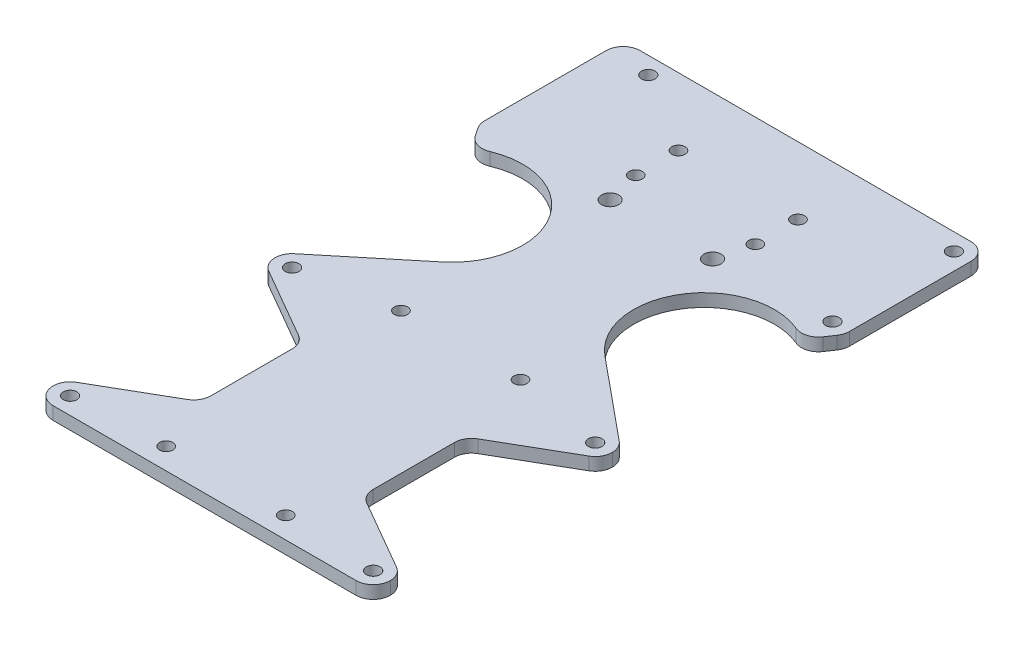
SolidWorks part; units mm, degrees
material "Thornel Mat VMA"
ref_plane "Front Plane" through (0, 0, 0) normal (0, 0, 1) x (1, 0, 0)
ref_plane "Top Plane" through (0, 0, 0) normal (0, 1, 0) x (1, 0, 0)
ref_plane "Right Plane" through (0, 0, 0) normal (1, 0, 0) x (0, 0, -1)
sketch "Sketch1" plane through (0, 0, 0) normal (0, 1, 0) x (1, 0, 0)
  line L0 (0, 0) -> (0, -82.5) construction
  line L1 (29.5, 0) -> (0, 0) construction
  line L19 (14, -27.5) -> (-14, -27.5) construction
  line L22 (14, -27.5) -> (14, 27.5) construction
  line L25 (14, 27.5) -> (-14, 27.5) construction
  line L28 (-14, -27.5) -> (-14, 27.5) construction
  line L38 (14, -27.5) -> (-14, 27.5) construction
  line L41 (47.5, 62.5) -> (-47.5, 62.5)
  line L44 (47.5, 62.5) -> (47.5, -87.5)
  line L47 (47.5, -87.5) -> (-47.5, -87.5)
  line L50 (-47.5, 62.5) -> (-47.5, -87.5)
  line L59 (-959, -57) -> (49041, -57) construction
  line L65 (14, 27.5) -> (-14, -27.5) construction
  line L66 (-14, 37.5) -> (14, 37.5) construction
  line L67 (-14, 37.5) -> (-14, 27.5) construction
  line L69 (14, 37.5) -> (14, 27.5) construction
  line L74 (-14, -27.5) -> (-14, -82.5) construction
  line L75 (-14, -82.5) -> (14, -82.5) construction
  line L76 (14, -82.5) -> (14, -27.5) construction
  line L94 (0, -82.5) -> (0, -87.5) construction
  circle A0 centre (29.5, 0) radius 16.5
  circle A22 centre (14, 27.5) radius 1.55
  circle A23 centre (14, -27.5) radius 1.55
  circle A24 centre (-14, -27.5) radius 1.55
  circle A25 centre (-14, 27.5) radius 1.55
  circle A76 centre (-14, 37.5) radius 1.55
  circle A77 centre (14, 37.5) radius 1.55
  circle A91 centre (-14, -82.5) radius 1.55
  circle A92 centre (14, -82.5) radius 1.55
  circle A99 centre (-29.5, 0) radius 16.5
  point P1 (0, -53.5)
  point P37 (29.5, 0)
  point P51 (0, 32.5)
  dimension "D1" = 33
  dimension "D6" = 25
  dimension "D7" = 5
  dimension "D10" = 3.1
  dimension "D12" = 55
  dimension "D15" = 10
  dimension "D19" = 28
  dimension "D20" = 29.5
  dimension "D3" = 95
  dimension "D14" = 55
extrude "凸台-拉伸1" add sketch "Sketch1" along normal blind 3 contours L41 L50 L47 L44 A23 A22 A0 region at (0, 0, 14.2195)
sketch "草图9" plane through (0, 0, 0) normal (0, 1, 0) x (1, 0, 0)
  line L0 (0, 35) -> (0, 0) construction
  line L1 (42.55, 7.5) -> (-42.55, 7.5) construction
  line L2 (42.55, 7.5) -> (42.55, 62.5) construction
  line L3 (42.55, 62.5) -> (-42.55, 62.5) construction
  line L4 (-42.55, 7.5) -> (-42.55, 62.5) construction
  line L5 (42.55, 7.5) -> (-42.55, 62.5) construction
  line L6 (42.55, 62.5) -> (-42.55, 7.5) construction
  line L7 (-32.84, 49.29) -> (38.74, 49.29) construction
  line L8 (38.74, 49.29) -> (38.74, 20.84) construction
  circle A0 centre (-14, 27.5) radius 1.55 construction
  circle A1 centre (38.74, 20.84) radius 1.6
  circle A2 centre (38.74, 49.29) radius 1.6
  circle A3 centre (-32.84, 49.29) radius 1.6
  point P0 (0, 35)
  dimension "D6" = 3.2
  dimension "D1" = 55
  dimension "D2" = 85.1
  dimension "D3" = 20
  dimension "D4" = 3.81
  dimension "D5" = 13.21
  dimension "D7" = 13.34
  dimension "D8" = 9.71
extrude "主控板固定孔" cut sketch "草图9" along normal up to next
sketch "草图10" plane through (0, 0, 0) normal (0, 1, 0) x (1, 0, 0)
  line L0 (0, 0) -> (0, -57.5) construction
  line L1 (35.5, -83.5) -> (-35.5, -83.5) construction
  line L2 (35.5, -83.5) -> (35.5, -31.5) construction
  line L3 (35.5, -31.5) -> (-35.5, -31.5) construction
  line L4 (-35.5, -83.5) -> (-35.5, -31.5) construction
  line L5 (35.5, -83.5) -> (-35.5, -31.5) construction
  line L6 (35.5, -31.5) -> (-35.5, -83.5) construction
  line L7 (47.5, -87.5) -> (-47.5, -87.5) construction
  circle A0 centre (35.5, -31.5) radius 1.6
  circle A1 centre (35.5, -83.5) radius 1.6
  circle A2 centre (-35.5, -31.5) radius 1.6
  circle A3 centre (-35.5, -83.5) radius 1.6
  point P0 (0, -57.5)
  dimension "D1" = 4
  dimension "D2" = 3.2
  dimension "D3" = 52
  dimension "D4" = 71
extrude "图传固定孔" cut sketch "草图10" along normal up to next
sketch "草图11" plane through (0, 0, 0) normal (0, 1, 0) x (1, 0, 0)
  line L0 (0, 0) -> (0, 22.5) construction
  line L1 (9, -22.5) -> (-9, -22.5) construction
  line L2 (9, -22.5) -> (9, 22.5) construction
  line L3 (9, 22.5) -> (-9, 22.5) construction
  line L4 (-9, -22.5) -> (-9, 22.5) construction
  line L5 (9, -22.5) -> (-9, 22.5) construction
  line L6 (9, 22.5) -> (-9, -22.5) construction
  circle A0 centre (-29.5, 0) radius 22.5 construction
  circle A1 centre (-14, 27.5) radius 1.55 construction
  circle A2 centre (-12, 19.5) radius 2
  circle A3 centre (12, 19.5) radius 2
  point P3 (0, 0)
  dimension "D1" = 45
  dimension "D4" = 4
  dimension "D2" = 18
  dimension "D3" = 5
  dimension "D5" = 3
  dimension "D6" = 3
extrude "光电二极管留孔" cut sketch "草图11" along normal up to next
sketch "草图8" plane through (0, 0, 0) normal (0, 1, 0) x (1, 0, 0)
  line L3 (47.5, 62.5) -> (47.5, -87.5)
  line L13 (0, 62.5) -> (0, -87.5) construction
  line L14 (0, 62.5) -> (0, 53.29)
  line L15 (47.5, 62.5) -> (-47.5, 62.5) construction
  line L16 (47.5, -87.5) -> (-47.5, -87.5) construction
  line L17 (0, 62.5) -> (47.5, 62.5)
  line L18 (0, 53.29) -> (42.74, 53.29)
  line L20 (42.74, 53.29) -> (42.74, 19.6164)
  line L23 (39.5, -29.6125) -> (39.5, -33.8094)
  line L27 (47.5, -87.5) -> (39.5, -87.5)
  line L28 (42.74, 19.6164) -> (29.5, 0)
  line L32 (19.01, -12.7362) -> (39.5, -29.6125)
  line L37 (39.5, -33.8094) -> (19, -45.6451)
  line L38 (19, -45.6451) -> (19, -69.3549)
  line L39 (19, -69.3549) -> (39.5, -81.1906)
  line L40 (19, -57.5) -> (-1.5333, -57.5) construction
  line L41 (-1.5333, -57.5) -> (19, -45.6451) construction
  line L42 (19, -69.3549) -> (-1.5333, -57.5) construction
  line L43 (39.5, -81.1906) -> (39.5, -87.5)
  line L44 (29.5, 0) -> (19.01, -12.7362)
  circle A0 centre (14, -82.5) radius 1.55 construction
  circle A2 centre (38.74, 49.29) radius 1.6 construction
  circle A3 centre (38.74, 20.84) radius 1.6 construction
  circle A4 centre (29.5, 0) radius 16.5 construction
  circle A5 centre (35.5, -83.5) radius 1.6 construction
  circle A6 centre (35.5, -31.5) radius 1.6 construction
  dimension "D1" = 4
  dimension "D2" = 4
  dimension "D3" = 4
  dimension "D4" = 4
  dimension "D6" = 4
  dimension "D7" = 5
  dimension "D5" = 4
  dimension "D8" = 60
  dimension "D9" = 4
extrude "板型" cut sketch "草图8" along normal up to next contours L17 L3 L27 L43 L39 L38 L37 L23 L32 L44 L28 L20 L18 L14
mirror "镜向1" about plane through (0, 0, 0) normal (1, 0, 0) of "板型"
fillet "圆角1" radius 4 18 edges at (-39.5, 1.5, 29.6125) (-38.7308, 1.5, -13.6764) (-42.74, 1.5, -19.6164) (-42.74, 1.5, -53.29) (42.74, 1.5, -53.29) (42.74, 1.5, -19.6164) (38.7308, 1.5, -13.6764) (39.5, 1.5, 29.6125) (-39.5, 1.5, 81.1906) (-19, 1.5, 69.3549) (-19, 1.5, 45.6451) (-39.5, 1.5, 33.8094) (39.5, 1.5, 33.8094) (19, 1.5, 45.6451) (19, 1.5, 69.3549) (39.5, 1.5, 81.1906) (39.5, 1.5, 87.5) (-39.5, 1.5, 87.5)
fillet "圆角2" [suppressed] radius 5
